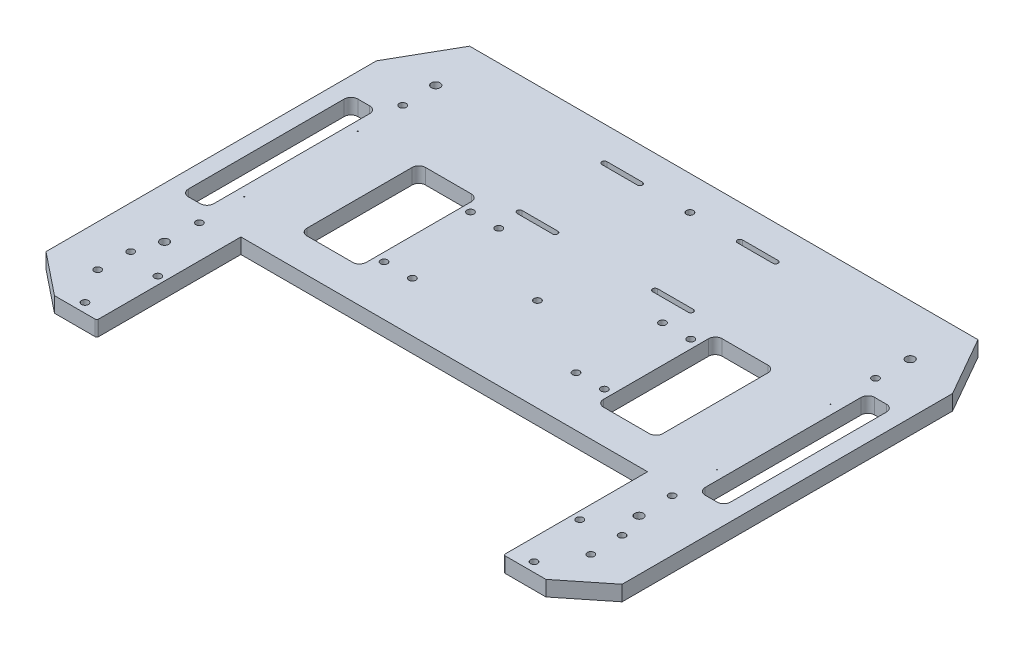
SolidWorks part; units mm, degrees
ref_plane "Plan de face" through (0, 0, 0) normal (0, 0, 1) x (1, 0, 0)
ref_plane "Plan de dessus" through (0, 0, 0) normal (0, 1, 0) x (1, 0, 0)
ref_plane "Plan de droite" through (0, 0, 0) normal (1, 0, 0) x (0, 0, -1)
sketch "Esquisse3" plane through (0, 0, 0) normal (0, 1, 0) x (1, 0, 0)
  line L0 (-281.7629, 0) -> (308.2067, 0) construction
  line L1 (0, 166.4902) -> (0, -269.1166) construction
  line L4 (-160, -46) -> (-160, 46)
  line L5 (-156, 50) -> (-149, 50)
  line L6 (-145, 46) -> (-145, -46)
  line L7 (-105, 0) -> (-105, 31)
  line L8 (-101, 35) -> (-74, 35)
  line L9 (-70, 31) -> (-70, -31)
  line L11 (-105, 0) -> (-105, -31)
  line L12 (-101, -35) -> (-74, -35)
  line L13 (-156, -50) -> (-149, -50)
  line L17 (156, 50) -> (149, 50)
  line L18 (156, -50) -> (149, -50)
  line L19 (145, 46) -> (145, -46)
  line L20 (160, -46) -> (160, 46)
  line L21 (105, 0) -> (105, 31)
  line L22 (101, -35) -> (74, -35)
  line L23 (105, 0) -> (105, -31)
  line L24 (70, 31) -> (70, -31)
  line L25 (101, 35) -> (74, 35)
  line L26 (150, 110) -> (-150, 110)
  line L34 (-170, 75) -> (-150, 110)
  line L35 (170, 75) -> (150, 110)
  line L38 (-170, 75) -> (-170, 0)
  line L39 (-170, 0) -> (-170, -120)
  line L40 (170, -120) -> (170, 0)
  line L41 (170, 0) -> (170, 75)
  line L43 (-170, -120) -> (-145, -140)
  line L44 (145, -140) -> (170, -120)
  line L45 (-145, -140) -> (-120, -140)
  line L46 (-120, -140) -> (-120, -55)
  line L47 (-120, -55) -> (120, -55)
  line L48 (120, -55) -> (120, -140)
  line L49 (120, -140) -> (145, -140)
  line L50 (-170, 75) -> (170, 75) construction
  line L51 (-170, 0) -> (-220, 0) construction
  line L52 (-220, 0) -> (-170, 75) construction
  line L53 (-220, 0) -> (-170, -120) construction
  line L54 (-130, -140) -> (-130, -220) construction
  line L55 (-130, -220) -> (130, -220) construction
  line L56 (130, -140) -> (130, -220) construction
  line L57 (-170, -120) -> (-130, -220) construction
  line L58 (-170, 0) -> (-200, 0) construction
  line L60 (-150, 90) -> (-130, 90) construction
  line L61 (-150, 90) -> (-150, 70) construction
  line L62 (-150, 70) -> (-130, 70) construction
  line L63 (-130, 90) -> (-130, 70) construction
  line L64 (-150, 90) -> (-130, 70) construction
  line L65 (-150, 70) -> (-130, 90) construction
  arc A0 (-149, 50) -> (-145, 46) centre (-149, 46) cw
  arc A1 (-74, 35) -> (-70, 31) centre (-74, 31) cw
  arc A2 (-105, 31) -> (-101, 35) centre (-101, 31) cw
  arc A3 (-160, 46) -> (-156, 50) centre (-156, 46) cw
  arc A4 (-105, -31) -> (-101, -35) centre (-101, -31) ccw
  arc A5 (-74, -35) -> (-70, -31) centre (-74, -31) ccw
  arc A6 (-160, -46) -> (-156, -50) centre (-156, -46) ccw
  arc A7 (-149, -50) -> (-145, -46) centre (-149, -46) ccw
  arc A8 (149, 50) -> (145, 46) centre (149, 46) ccw
  arc A9 (160, 46) -> (156, 50) centre (156, 46) ccw
  arc A10 (149, -50) -> (145, -46) centre (149, -46) cw
  arc A11 (160, -46) -> (156, -50) centre (156, -46) cw
  arc A12 (74, -35) -> (70, -31) centre (74, -31) cw
  arc A13 (105, -31) -> (101, -35) centre (101, -31) cw
  arc A14 (105, 31) -> (101, 35) centre (101, 31) ccw
  arc A15 (74, 35) -> (70, 31) centre (74, 31) ccw
  circle A16 centre (-140, 80) radius 2.55
  circle A17 centre (-140, -80) radius 2.55
  circle A18 centre (140, -80) radius 2.55
  circle A19 centre (140, 80) radius 2.55
  circle A20 centre (0, 0) radius 200 construction
  circle A21 centre (0, 0) radius 185.809 construction
  point P6 (-170, 110)
  point P16 (-105, 15.5)
  point P19 (-145, 50)
  point P22 (-70, 35)
  point P25 (-105, 35)
  point P28 (-160, 50)
  point P32 (-70, 0)
  point P37 (-105, -35)
  point P38 (-70, -35)
  point P40 (-145, 0)
  point P41 (-160, 0)
  point P45 (-160, -50)
  point P46 (-145, -50)
  point P47 (0, 110)
  point P48 (-170, 0)
  point P51 (0, -110)
  point P64 (145, -50)
  point P65 (160, -50)
  point P75 (70, -35)
  point P76 (105, -35)
  point P81 (105, 35)
  point P82 (70, 35)
  point P83 (0, -269.1166)
  point P85 (0, 110)
  point P94 (-170, 0)
  point P97 (170, 0)
  point P100 (0, -130)
  dimension "D7" = 4
  dimension "D10" = 5.1
  dimension "D32" = 30
  dimension "D33" = 400
  dimension "D34" = 371.6181
  dimension "D2" = 300
  dimension "D3" = 35
  dimension "D4" = 15
  dimension "D5" = 70
  dimension "D6" = 40
  dimension "D14" = 25
  dimension "D13" = 110
  dimension "D8" = 35
  dimension "D9" = 50
  dimension "D11" = 240
  dimension "D12" = 340
  dimension "D15" = 120
  dimension "D16" = 75
  dimension "D17" = 140
  dimension "D18" = 80
  dimension "D19" = 85
  dimension "D20" = 140
  dimension "D21" = 150
  dimension "D22" = 32.0156
  dimension "D23" = 40.3113
  dimension "D24" = 120
  dimension "D25" = 50
  dimension "D26" = 130
  dimension "D27" = 90.1388
  dimension "D28" = 80
  dimension "D29" = 10
  dimension "D30" = 107.7033
  dimension "D31" = 130
  dimension "D35" = 20
extrude "structure" add sketch "Esquisse3" against normal blind 9
sketch "Esquisse4" plane through (0, 0, 0) normal (0, 1, 0) x (1, 0, 0)
  line L0 (-232.6304, 0) -> (230.9735, 0) construction
  line L1 (0, 112.1729) -> (0, -129.4048) construction
  line L3 (-145, -46) -> (-145, 46) construction
  line L12 (-150, 110) -> (-170, 75)
  line L13 (-170, 75) -> (-170, -120)
  line L14 (-170, -120) -> (-145, -140)
  line L15 (-120, -55) -> (120, -55)
  line L16 (145, -140) -> (170, -120)
  line L17 (170, -120) -> (170, 75)
  line L18 (170, 75) -> (150, 110)
  line L19 (150, 110) -> (-150, 110)
  line L20 (-150, 110) -> (-170, 75)
  line L21 (-170, 75) -> (-170, -120)
  line L22 (-170, -120) -> (-145, -140)
  line L24 (145, -140) -> (170, -120)
  line L25 (170, -120) -> (170, 75)
  line L26 (170, 75) -> (150, 110)
  line L27 (150, 110) -> (-150, 110)
  line L32 (-120, -55) -> (120, -55)
  line L33 (120, -55) -> (120, -140)
  line L34 (120, -55) -> (120, -140)
  line L35 (120, -140) -> (145, -140)
  line L36 (120, -140) -> (145, -140)
  line L37 (-145, -140) -> (-120, -140)
  line L38 (-145, -140) -> (-120, -140)
  line L39 (-120, -140) -> (-120, -55)
  line L40 (-120, -140) -> (-120, -55)
  circle A0 centre (-139.5, 33.5) radius 0.25
  circle A2 centre (-139.5, -33.5) radius 0.25
  circle A3 centre (139.5, -33.5) radius 0.25
  circle A4 centre (139.5, 33.5) radius 0.25
  dimension "D1" = 0.5
  dimension "D2" = 0
  dimension "D3" = 33.5
  dimension "D4" = 5.5
extrude "encoches_tiges" cut sketch "Esquisse4" against normal blind 5 contours A3 | A4 | A2 | A0
sketch "Esquisse5" plane through (0, 0, 0) normal (0, 1, 0) x (1, 0, 0)
  line L0 (-244.8916, 0) -> (242.9033, 0) construction
  line L1 (0, 111.8416) -> (0, -134.3756) construction
  line L3 (-145, -46) -> (-145, 46) construction
  line L12 (-150, 110) -> (-170, 75)
  line L13 (-170, 75) -> (-170, -120)
  line L14 (-170, -120) -> (-145, -140)
  line L15 (-120, -55) -> (120, -55)
  line L16 (145, -140) -> (170, -120)
  line L17 (170, -120) -> (170, 75)
  line L18 (170, 75) -> (150, 110)
  line L19 (150, 110) -> (-150, 110)
  line L20 (-150, 110) -> (-170, 75)
  line L21 (-170, 75) -> (-170, -120)
  line L22 (-170, -120) -> (-145, -140)
  line L24 (145, -140) -> (170, -120)
  line L25 (170, -120) -> (170, 75)
  line L26 (170, 75) -> (150, 110)
  line L27 (150, 110) -> (-150, 110)
  line L32 (-120, -55) -> (120, -55)
  line L33 (120, -55) -> (120, -140)
  line L34 (120, -55) -> (120, -140)
  line L35 (120, -140) -> (145, -140)
  line L36 (120, -140) -> (145, -140)
  line L37 (-145, -140) -> (-120, -140)
  line L38 (-145, -140) -> (-120, -140)
  line L39 (-120, -140) -> (-120, -55)
  line L40 (-120, -140) -> (-120, -55)
  circle A0 centre (-139.5, 60) radius 2.05
  circle A1 centre (-139.5, -60) radius 2.05
  circle A2 centre (139.5, -60) radius 2.05
  circle A3 centre (139.5, 60) radius 2.05
  dimension "D3" = 4.1
  dimension "D1" = 60
  dimension "D2" = 0
  dimension "D4" = 5.5
extrude "encodeurs" cut sketch "Esquisse5" against normal through all contours A1 | A0 | A3 | A2
sketch "Esquisse6" plane through (0, 0, 0) normal (0, 1, 0) x (1, 0, 0)
  line L0 (0, 109.8533) -> (0, -117.4751) construction
  line L1 (-179.2779, 0) -> (195.847, 0) construction
  line L2 (-98.5767, 25.5) -> (7.2216, 25.5) construction
  line L4 (-70, -31) -> (-70, 31) construction
  line L12 (-150, 110) -> (-170, 75)
  line L13 (-170, 75) -> (-170, -120)
  line L14 (-170, -120) -> (-145, -140)
  line L15 (-120, -55) -> (120, -55)
  line L16 (145, -140) -> (170, -120)
  line L17 (170, -120) -> (170, 75)
  line L18 (170, 75) -> (150, 110)
  line L19 (150, 110) -> (-150, 110)
  line L20 (-150, 110) -> (-170, 75)
  line L21 (-170, 75) -> (-170, -120)
  line L22 (-170, -120) -> (-145, -140)
  line L24 (145, -140) -> (170, -120)
  line L25 (170, -120) -> (170, 75)
  line L26 (170, 75) -> (150, 110)
  line L27 (150, 110) -> (-150, 110)
  line L33 (-120, -55) -> (120, -55)
  line L34 (120, -55) -> (120, -140)
  line L35 (120, -55) -> (120, -140)
  line L36 (120, -140) -> (145, -140)
  line L37 (120, -140) -> (145, -140)
  line L38 (-145, -140) -> (-120, -140)
  line L39 (-145, -140) -> (-120, -140)
  line L40 (-120, -140) -> (-120, -55)
  line L41 (-120, -140) -> (-120, -55)
  circle A0 centre (-65, 25.5) radius 2.05
  circle A1 centre (-48.3, 25.5) radius 2.05
  circle A2 centre (-48.3, -25.5) radius 2.05
  circle A3 centre (-65, -25.5) radius 2.05
  circle A4 centre (65, -25.5) radius 2.05
  circle A5 centre (48.3, -25.5) radius 2.05
  circle A6 centre (48.3, 25.5) radius 2.05
  circle A7 centre (65, 25.5) radius 2.05
  dimension "D1" = 4.1
  dimension "D2" = 4.1
  dimension "D3" = 16.7
  dimension "D4" = 25.5
  dimension "D5" = 0
  dimension "D6" = 5
extrude "moteurs" cut sketch "Esquisse6" against normal through all both and the other way through all contours A0 | A1 | A3 | A5 | A4 | A2 | A6 | A7 | A3 region at (-65, 0, -25.5) region at (-48.3, 0, -25.5) region at (-65, 0, 25.5) region at (65, 0, 25.5) region at (48.3, 0, 25.5)
sketch "Esquisse7" plane through (0, 0, 0) normal (0, 1, 0) x (1, 0, 0)
  line L0 (-174.1619, -95) -> (241.5194, -95) construction
  line L2 (0, -145.9077) -> (0, 135.7674) construction
  line L3 (-194.9191, 0) -> (209.9418, 0) construction
  circle A0 centre (0, 90) radius 2.05
  circle A1 centre (0, -90) radius 2.05 construction
  circle A2 centre (0, 0) radius 2.05
  circle A3 centre (-145, -95) radius 2.05
  circle A4 centre (145, -95) radius 2.05
  dimension "D1" = 4.1
  dimension "D3" = 4.1
  dimension "D5" = 145
  dimension "D2" = 90
  dimension "D4" = 95
extrude "patins" cut sketch "Esquisse7" against normal through all
sketch "Esquisse8" plane through (0, 0, 0) normal (0, 1, 0) x (1, 0, 0)
  line L0 (0, 136.7319) -> (0, -163.5964) construction
  line L13 (-120, -55) -> (120, -55)
  line L14 (-120, -55) -> (120, -55)
  line L15 (120, -55) -> (120, -140)
  line L16 (120, -55) -> (120, -140)
  line L17 (120, -140) -> (145, -140)
  line L18 (120, -140) -> (145, -140)
  line L19 (145, -140) -> (170, -120)
  line L20 (145, -140) -> (170, -120)
  line L21 (170, -120) -> (170, 75)
  line L22 (170, -120) -> (170, 75)
  line L23 (170, 75) -> (150, 110)
  line L24 (170, 75) -> (150, 110)
  line L37 (150, 110) -> (-150, 110)
  line L38 (150, 110) -> (-150, 110)
  line L39 (-150, 110) -> (-170, 75)
  line L40 (-150, 110) -> (-170, 75)
  line L41 (-170, 75) -> (-170, -120)
  line L42 (-170, 75) -> (-170, -120)
  line L43 (-170, -120) -> (-145, -140)
  line L44 (-170, -120) -> (-145, -140)
  line L45 (-145, -140) -> (-120, -140)
  line L46 (-145, -140) -> (-120, -140)
  line L47 (-120, -140) -> (-120, -55)
  line L48 (-120, -140) -> (-120, -55)
  circle A0 centre (-132.5, -134.5) radius 2.05
  circle A1 centre (-124.5, -99.5) radius 2.05
  circle A2 centre (132.5, -134.5) radius 2.05
  circle A3 centre (124.5, -99.5) radius 2.05
  circle A4 centre (-145.5, -114) radius 2.05
  circle A5 centre (145.5, -114) radius 2.05
  dimension "D2" = 4.1
  dimension "D7" = 40.5
  dimension "D1" = 0
  dimension "D3" = 4.5
  dimension "D4" = 26
  dimension "D5" = 5.5
  dimension "D6" = 25.5
  dimension "D8" = 12.5
extrude "actionneurs" cut sketch "Esquisse8" against normal through all contours A1 | A0 | A3 | A2 | A4 | A5
fillet "Congé1" radius 1 2 edges at (120, -4.5, 140) (-120, -4.5, 140)
sketch "Esquisse9" plane through (0, 0, 0) normal (0, 1, 0) x (1, 0, 0)
  line L0 (-40, 126.0313) -> (-40, 26.6007) construction
  line L1 (-55.866, 65) -> (23.4115, 65) construction
  line L2 (-50.5, 90) -> (-29.5, 90) construction
  line L3 (-50.5, 91.5) -> (-29.5, 91.5)
  line L4 (-50.5, 88.5) -> (-29.5, 88.5)
  line L5 (-50.5, 40) -> (-29.5, 40) construction
  line L6 (-50.5, 38.5) -> (-29.5, 38.5)
  line L7 (-50.5, 41.5) -> (-29.5, 41.5)
  line L8 (0, 0) -> (0, 125.8879) construction
  line L9 (50.5, 40) -> (29.5, 40) construction
  line L10 (50.5, 38.5) -> (29.5, 38.5)
  line L11 (50.5, 41.5) -> (29.5, 41.5)
  line L12 (120, -55) -> (120, -139)
  line L13 (121, -140) -> (145, -140)
  line L14 (145, -140) -> (170, -120)
  line L15 (170, -120) -> (170, 75)
  line L16 (170, 75) -> (150, 110)
  line L17 (150, 110) -> (-150, 110)
  line L18 (-150, 110) -> (-170, 75)
  line L19 (-170, 75) -> (-170, -120)
  line L20 (-170, -120) -> (-145, -140)
  line L21 (-145, -140) -> (-121, -140)
  line L22 (-120, -139) -> (-120, -55)
  line L23 (-120, -55) -> (120, -55)
  line L24 (120, -55) -> (120, -139)
  line L25 (121, -140) -> (145, -140)
  line L26 (145, -140) -> (170, -120)
  line L27 (170, -120) -> (170, 75)
  line L28 (170, 75) -> (150, 110)
  line L29 (150, 110) -> (-150, 110)
  line L30 (-150, 110) -> (-170, 75)
  line L31 (-170, 75) -> (-170, -120)
  line L32 (-170, -120) -> (-145, -140)
  line L33 (-145, -140) -> (-121, -140)
  line L34 (-120, -139) -> (-120, -55)
  line L35 (-120, -55) -> (120, -55)
  line L36 (50.5, 90) -> (29.5, 90) construction
  line L37 (50.5, 91.5) -> (29.5, 91.5)
  line L38 (50.5, 88.5) -> (29.5, 88.5)
  line L39 (-70, 90) -> (-70, 54.007) construction
  arc A0 (-50.5, 91.5) -> (-50.5, 88.5) centre (-50.5, 90) ccw
  arc A1 (-29.5, 88.5) -> (-29.5, 91.5) centre (-29.5, 90) ccw
  arc A2 (120, -139) -> (121, -140) centre (121, -139) ccw
  arc A3 (-121, -140) -> (-120, -139) centre (-121, -139) ccw
  arc A4 (120, -139) -> (121, -140) centre (121, -139) ccw
  arc A5 (-121, -140) -> (-120, -139) centre (-121, -139) ccw
  arc A6 (-50.5, 38.5) -> (-50.5, 41.5) centre (-50.5, 40) cw
  arc A7 (-29.5, 41.5) -> (-29.5, 38.5) centre (-29.5, 40) cw
  arc A8 (50.5, 38.5) -> (50.5, 41.5) centre (50.5, 40) ccw
  arc A9 (29.5, 41.5) -> (29.5, 38.5) centre (29.5, 40) ccw
  arc A10 (50.5, 91.5) -> (50.5, 88.5) centre (50.5, 90) cw
  arc A11 (29.5, 88.5) -> (29.5, 91.5) centre (29.5, 90) cw
  point P17 (-40, 90)
  point P29 (-40, 40)
  point P39 (40, 40)
  point P46 (40, 90)
  dimension "D2" = 3
  dimension "D3" = 21
  dimension "D4" = 25
  dimension "D5" = 65
  dimension "D6" = 40
  dimension "D7" = 70
  dimension "D1" = 0
extrude "batterie" cut sketch "Esquisse9" against normal blind 30 contours A11 L38 A10 L37 | L4 A1 L3 A0 | L6 A7 L7 A6 | L10 A9 L11 A8 region at (40, 0, -90)
